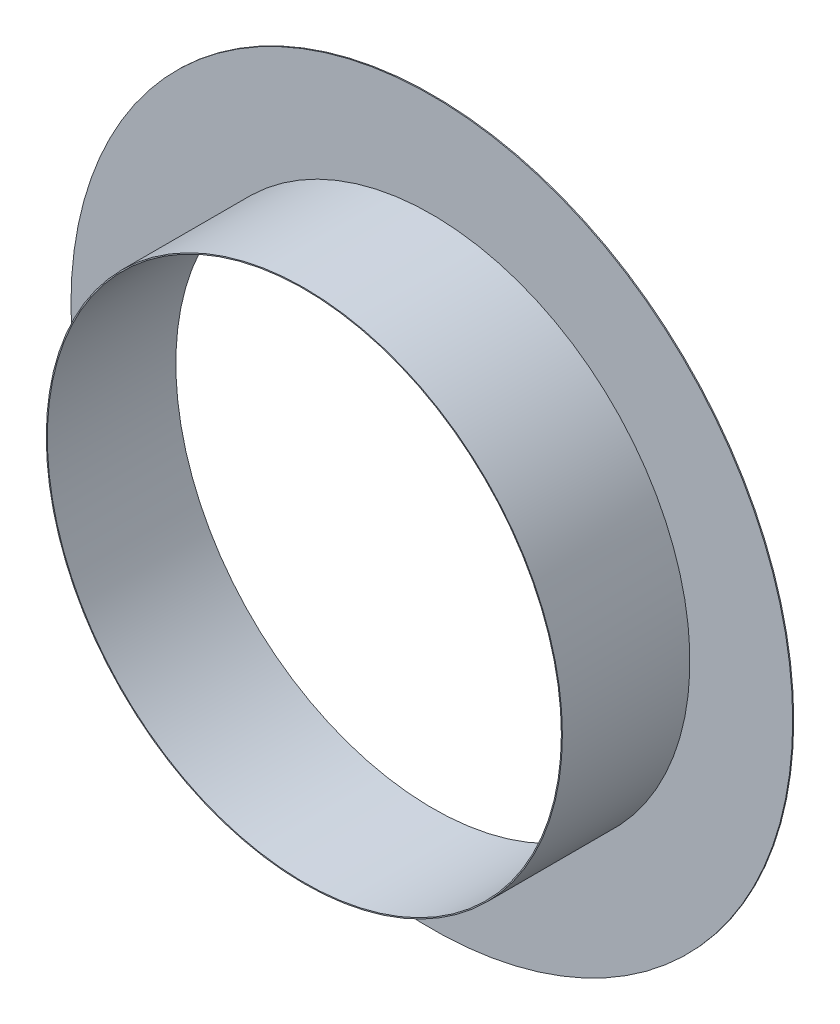
SolidWorks part; units mm, degrees
material "Plain Carbon Steel"
ref_plane "Front Plane" through (0, 0, 0) normal (0, 0, 1) x (1, 0, 0)
ref_plane "Top Plane" through (0, 0, 0) normal (0, 1, 0) x (1, 0, 0)
ref_plane "Right Plane" through (0, 0, 0) normal (1, 0, 0) x (0, 0, -1)
sketch "Sketch1" plane through (0, 0, 0) normal (0, 0, 1) x (1, 0, 0)
  circle A0 centre (0, 0) radius 500
  dimension "Diameter" = 1000
extrude "Extrude-Thin1" add sketch "Sketch1" along normal blind 250 thin thin type one direction wall 2
sketch "Sketch2" plane through (0, 0, 0) normal (0, 0, -1) x (-1, 0, 0)
  circle A0 centre (0, 0) radius 502 construction
  circle A1 centre (0, 0) radius 502
  circle A2 centre (0, 0) radius 702
  dimension "FlangeHeight" = 200
extrude "Boss-Extrude2" add sketch "Sketch2" against normal blind 2
sketch "Sketch3" plane through (0, 0, 0) normal (0, 0, 1) x (1, 0, 0)
  point P0 (0, 0)
other "CPoint1" parameters "Diameter"=1000, "StubLength"=1000
ref_axis "Axis1" through (0, 0, 10) along (0, 0, -1)
